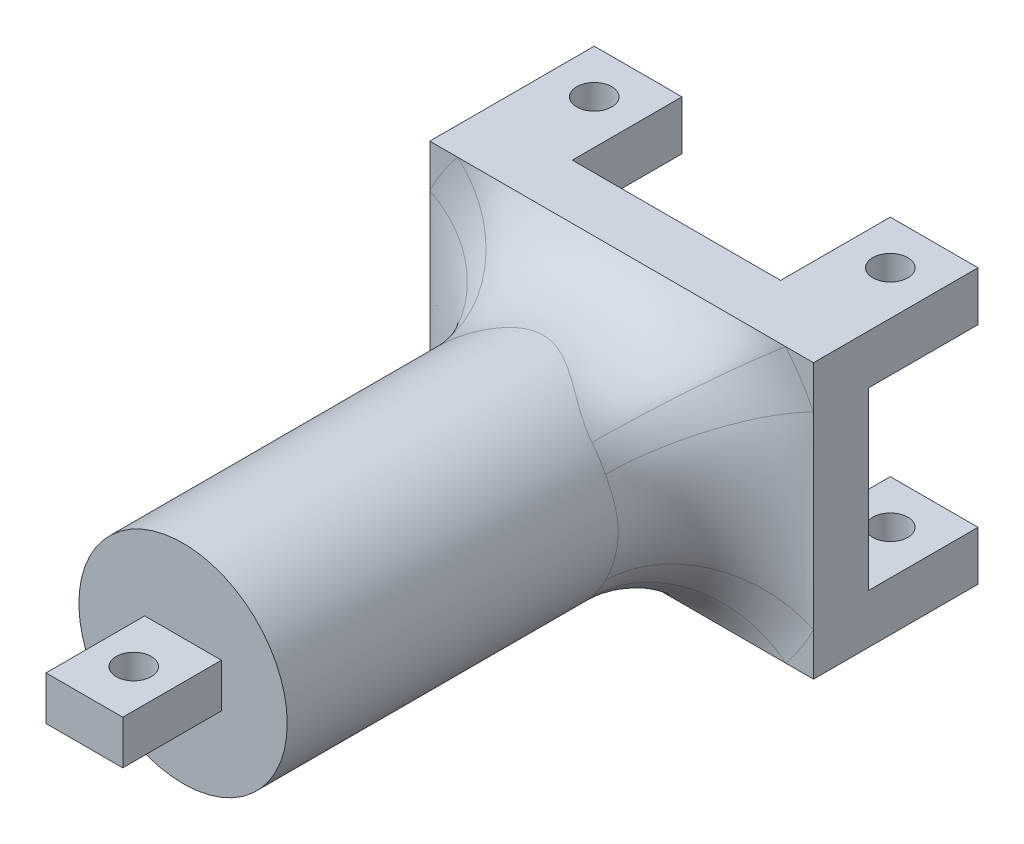
SolidWorks part; units mm, degrees
ref_plane "Plan de face" through (0, 0, 0) normal (0, 0, 1) x (1, 0, 0)
ref_plane "Plan de dessus" through (0, 0, 0) normal (0, 1, 0) x (1, 0, 0)
ref_plane "Plan de droite" through (0, 0, 0) normal (1, 0, 0) x (0, 0, -1)
ref_plane "Plan1" through (0, 0, -5) normal (0, 0, -1) x (-1, 0, 0)
sketch "Esquisse1" plane through (0, 0, -5) normal (0, 0, -1) x (-1, 0, 0)
  line L0 (-17.5, 12.5) -> (-17.5, -12.5)
  line L1 (-17.5, -12.5) -> (17.5, -12.5)
  line L2 (17.5, -12.5) -> (17.5, 12.5)
  line L3 (17.5, 12.5) -> (-17.5, 12.5)
extrude "Boss.-Extru.1" add sketch "Esquisse1" against normal blind 5
sketch "Esquisse2" plane through (0, 0, -5) normal (0, 0, -1) x (-1, 0, 0)
  line L0 (17.5, -8) -> (17.5, -12.5)
  line L1 (17.5, -12.5) -> (9.5, -12.5)
  line L2 (9.5, -12.5) -> (9.5, -8)
  line L3 (9.5, -8) -> (17.5, -8)
extrude "Boss.-Extru.2" add sketch "Esquisse2" along normal blind 10
sketch "Esquisse3" plane through (0, 0, -5) normal (0, 0, -1) x (-1, 0, 0)
  line L0 (17.5, 12.5) -> (17.5, 8)
  line L1 (17.5, 8) -> (9.5, 8)
  line L2 (9.5, 8) -> (9.5, 12.5)
  line L3 (9.5, 12.5) -> (17.5, 12.5)
extrude "Boss.-Extru.3" add sketch "Esquisse3" along normal blind 10
sketch "Esquisse4" plane through (0, 0, -5) normal (0, 0, -1) x (-1, 0, 0)
  line L0 (-17.5, 8) -> (-17.5, 12.5)
  line L1 (-17.5, 12.5) -> (-9.5, 12.5)
  line L2 (-9.5, 12.5) -> (-9.5, 8)
  line L3 (-9.5, 8) -> (-17.5, 8)
extrude "Boss.-Extru.4" add sketch "Esquisse4" along normal blind 10
sketch "Esquisse5" plane through (0, 0, -5) normal (0, 0, -1) x (-1, 0, 0)
  line L0 (-17.5, -12.5) -> (-17.5, -8)
  line L1 (-17.5, -8) -> (-9.5, -8)
  line L2 (-9.5, -8) -> (-9.5, -12.5)
  line L3 (-9.5, -12.5) -> (-17.5, -12.5)
extrude "Boss.-Extru.5" add sketch "Esquisse5" along normal blind 10
sketch "Esquisse6" plane through (0, 0, 0) normal (0, 0, 1) x (1, 0, 0)
  circle A0 centre (0, 0) radius 9.5
extrude "Boss.-Extru.6" add sketch "Esquisse6" along normal blind 40
sketch "Esquisse7" plane through (0, 0, 40) normal (0, 0, 1) x (1, 0, 0)
  line L0 (-3.5, 2) -> (3.5, 2)
  line L1 (3.5, 2) -> (3.5, -2)
  line L2 (3.5, -2) -> (-3.5, -2)
  line L3 (-3.5, -2) -> (-3.5, 2)
extrude "Boss.-Extru.7" add sketch "Esquisse7" along normal blind 9
hole_wizard "Diamètre du perçage Ø3.2 (3.2)1" positions "Esquisse9" profile "Esquisse8" hole size "Ø3.2" standard "Ansi Metric"
sketch "Esquisse9" plane through (0, 2, 0) normal (0, 1, 0) x (1, 0, 0)
  point P0 (0, -44.5)
sketch "Esquisse8" plane through (0, 2, 44.5) normal (1, 0, 0) x (0, 0, 1)
  line L0 (0, 0) -> (0, 14.5)
  line L1 (0, 14.5) -> (1.6, 14.5)
  line L2 (1.6, 14.5) -> (1.6, 0)
  line L5 (1.6, 0) -> (0, 0)
  line L11 (0, -6.35) -> (0, 107.95) construction
  dimension "Diamètre du perçage jusqu'au prochain" = 3.2
  dimension "Profondeur du perçage jusqu'au prochain" = 14.5
hole_wizard "Diamètre du perçage Ø3.2 (3.2)2" positions "Esquisse11" profile "Esquisse10" hole size "Ø3.2" standard "Ansi Metric"
sketch "Esquisse11" plane through (0, 8, 0) normal (0, -1, 0) x (-1, 0, 0)
  point P0 (-13.5, 11)
  point P1 (13.5, 11)
sketch "Esquisse10" plane through (13.5, 8, -11) normal (1, 0, 0) x (0, 0, -1)
  line L0 (0, 0) -> (0, 4.5)
  line L1 (0, 4.5) -> (1.6, 4.5)
  line L2 (1.6, 4.5) -> (1.6, 0)
  line L5 (1.6, 0) -> (0, 0)
  line L11 (0, -6.35) -> (0, 107.95) construction
  dimension "Diamètre du perçage jusqu'au prochain" = 3.2
  dimension "Profondeur du perçage jusqu'au prochain" = 4.5
hole_wizard "Diamètre du perçage Ø3.2 (3.2)3" positions "Esquisse13" profile "Esquisse12" hole size "Ø3.2" standard "Ansi Metric"
sketch "Esquisse13" plane through (0, -8, 0) normal (0, 1, 0) x (1, 0, 0)
  point P0 (13.5, 11)
  point P1 (-13.5, 11)
sketch "Esquisse12" plane through (13.5, -8, -11) normal (1, 0, 0) x (0, 0, 1)
  line L0 (0, 0) -> (0, 4.5)
  line L1 (0, 4.5) -> (1.6, 4.5)
  line L2 (1.6, 4.5) -> (1.6, 0)
  line L5 (1.6, 0) -> (0, 0)
  line L11 (0, -6.35) -> (0, 107.95) construction
  dimension "Diamètre du perçage jusqu'au prochain" = 3.2
  dimension "Profondeur du perçage jusqu'au prochain" = 4.5
fillet "Congé1" radius 10 1 edges at (9.5, 0, 0) tangent propagation no
